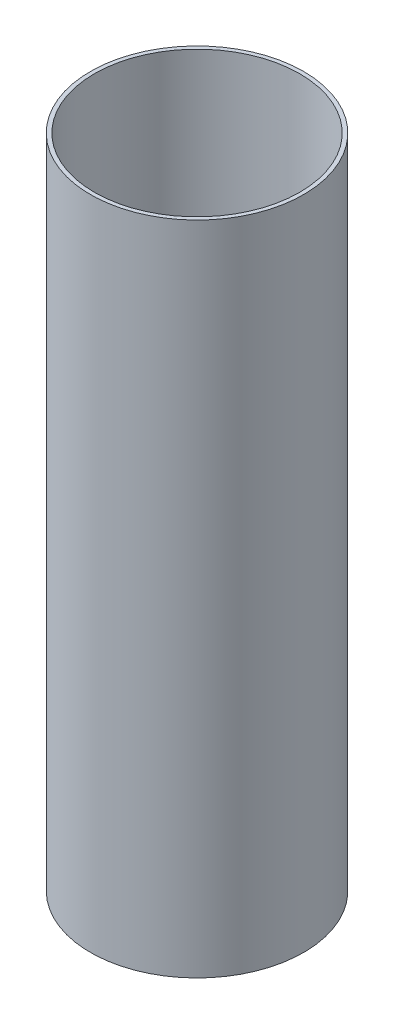
SolidWorks part; units mm, degrees
ref_plane "Front Plane" through (0, 0, 0) normal (0, 0, 1) x (1, 0, 0)
ref_plane "Top Plane" through (0, 0, 0) normal (0, 1, 0) x (1, 0, 0)
ref_plane "Right Plane" through (0, 0, 0) normal (1, 0, 0) x (0, 0, -1)
sketch "Sketch1" plane through (0, 0, 0) normal (0, 1, 0) x (1, 0, 0)
  circle A0 centre (0, 0) radius 49.5173
  circle A1 centre (0, 0) radius 47.6885
  dimension "D1" = 99.0346
  dimension "D2" = 95.377
extrude "Boss-Extrude1" add sketch "Sketch1" along normal blind 304.8
equation "\"Coupler_OD\"= 3.899in"
equation "\"Coupler_ID\"= 3.755in"
equation "\"Mid_Coupler_Length\"= 12in"
equation "\"D1@Sketch1\"=\"Coupler_OD\""
equation "\"D2@Sketch1\"=\"Coupler_ID\""
equation "\"D1@Boss-Extrude1\"=\"Mid_Coupler_Length\""
